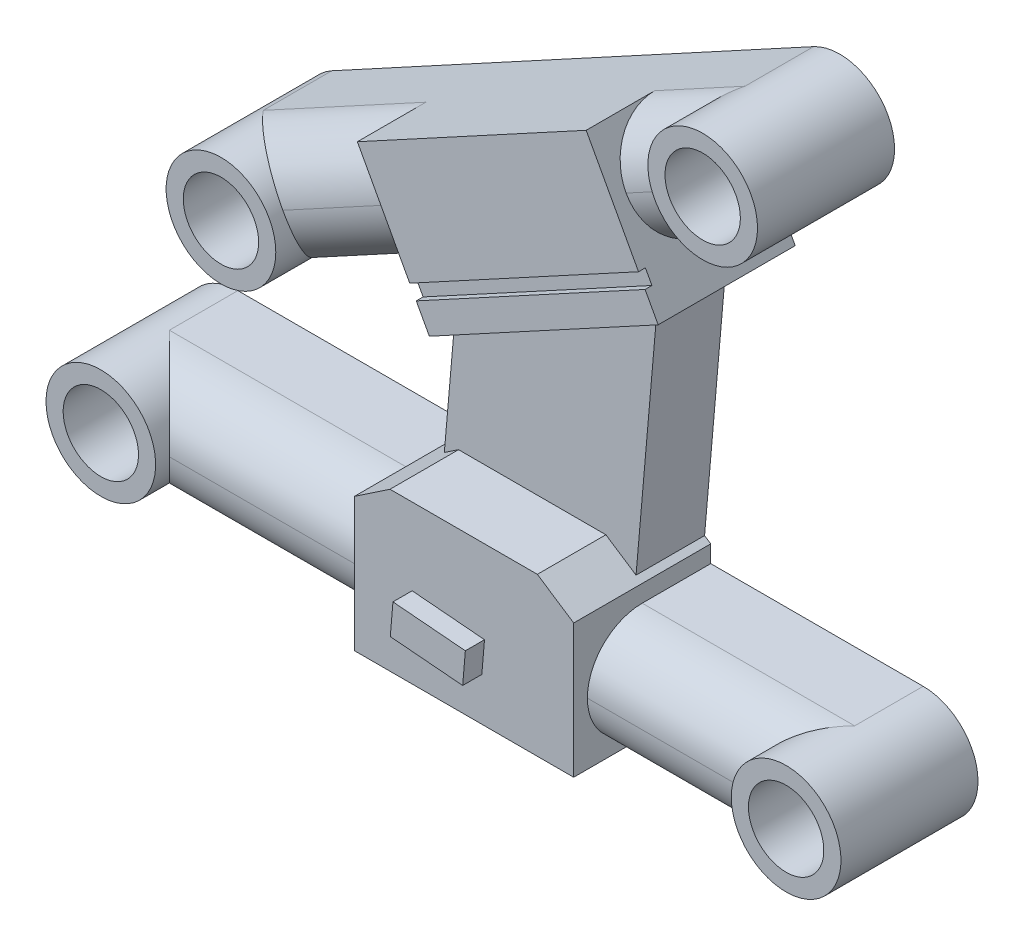
SolidWorks part; units mm, degrees
ref_plane "Front Plane" through (0, 0, 0) normal (0, 0, 1) x (1, 0, 0)
ref_plane "Top Plane" through (0, 0, 0) normal (0, 1, 0) x (1, 0, 0)
ref_plane "Right Plane" through (0, 0, 0) normal (1, 0, 0) x (0, 0, -1)
sketch "Sketch1" plane through (0, 0, 0) normal (0, 0, 1) x (1, 0, 0)
  line L0 (0, 0) -> (32, 0)
  line L1 (32, 0) -> (32, 19.5)
  line L2 (32, 19.5) -> (26.7, 23)
  line L3 (26.7, 23) -> (5.2, 23)
  line L4 (5.2, 23) -> (0, 19.5)
  line L5 (0, 19.5) -> (0, 0)
  dimension "D1" = 32
  dimension "D2" = 19.5
  dimension "D3" = 21.5
  dimension "D4" = 23
  dimension "D5" = 26.8
extrude "Boss-Extrude1" add sketch "Sketch1" along normal blind 20
sketch "Sketch2" plane through (0, 0, 0) normal (0, 0, -1) x (-1, 0, 0)
  line L0 (0, 0) -> (88.9399, 0) construction
  line L1 (88.9399, 0) -> (-120.0605, 0) construction
  line L2 (-32, 0) -> (-32, 19.5) construction
  line L3 (0, 19.5) -> (0, 0) construction
  circle A0 centre (-63, 9) radius 5.5
  circle A1 centre (-63, 9) radius 8
  circle A2 centre (37, 9) radius 5.5
  circle A3 centre (37, 9) radius 8
  dimension "D1" = 11
  dimension "D2" = 16
  dimension "D5" = 11
  dimension "D6" = 16
  dimension "D3" = 9
  dimension "D4" = 31
  dimension "D7" = 9
  dimension "D8" = 37
extrude "Boss-Extrude2" add sketch "Sketch2" against normal blind 20 separate body
sketch "Sketch4" plane through (32, 0, 0) normal (1, 0, 0) x (0, 0, -1)
  line L0 (0, 0) -> (0, 19.5) construction
  line L1 (0, 17) -> (-18, 17)
  line L2 (0, 17) -> (0, 1)
  line L3 (0, 1) -> (-18, 1)
  line L4 (-18, 17) -> (-18, 1)
  line L5 (-20, 19.5) -> (0, 19.5) construction
  dimension "D1" = 18
  dimension "D2" = 16
  dimension "D3" = 2.5
extrude "Boss-Extrude3" add sketch "Sketch4" along normal up to surface (31 mm away) up to face at (55, 9, 20)
sketch "Sketch5" plane through (0, 0, 0) normal (-1, 0, 0) x (0, 0, 1)
  line L0 (0, 19.5) -> (0, 0) construction
  line L1 (0, 17) -> (18, 17)
  line L2 (0, 17) -> (0, 1)
  line L3 (0, 1) -> (18, 1)
  line L4 (18, 17) -> (18, 1)
  line L5 (20, 19.5) -> (0, 19.5) construction
  dimension "D1" = 2.5
  dimension "D2" = 18
  dimension "D3" = 16
extrude "Boss-Extrude4" add sketch "Sketch5" along normal up to surface (37 mm away) up to face at (-45, 9, 20)
sketch "Sketch6" plane through (0, 0, 0) normal (0, 0, -1) x (-1, 0, 0)
  line L0 (-31.1, 20.0943) -> (-34.4, 57.9508)
  line L1 (-32, 19.5) -> (-26.7, 23) construction
  line L2 (-3.1254, 21.6036) -> (-5.9785, 54.3336)
  line L3 (-5.2, 23) -> (0, 19.5) construction
  line L4 (-10.9396, 45.2033) -> (-44.3289, 63.3458)
  line L5 (-44.3289, 63.3458) -> (-33.8254, 82.6765)
  line L6 (-33.8254, 82.6765) -> (-0.436, 64.5339)
  line L7 (-0.436, 64.5339) -> (-10.9396, 45.2033)
  line L8 (-32, 17) -> (-32, 19.5) construction
  line M11 (0, 19.5) -> (-5.2, 23)
  line M12 (-5.2, 23) -> (-26.7, 23)
  line M13 (-26.7, 23) -> (-32, 19.5)
  dimension "D1" = 28
  dimension "D2" = 0.9
  dimension "D3" = 38
  dimension "D4" = 2.4
  dimension "D5" = 38
  dimension "D6" = 22
  dimension "D7" = 123.5
  dimension "D8" = 11.3
extrude "Boss-Extrude5" add sketch "Sketch6" against normal blind 10 contours L2 L7 L4 L0 M13 M12 M11 region at (19.3948, 37.1745, 0)
extrude "Boss-Extrude6" add sketch "Sketch6<3>" against normal blind 20 contours L7 L6 L5 L4 region at (22.3825, 63.9399, 0)
sketch "Sketch6<3>" plane through (0, 0, 0) normal (0, 0, -1) x (-1, 0, 0) same geometry as "Sketch6"
sketch "Sketch7" plane through (0, 0, 20) normal (0, 0, 1) x (1, 0, 0)
  line L0 (-19.4685, 44.6138) -> (50.8248, 82.8087) construction
  line L3 (33.8254, 82.6765) -> (0.436, 64.5339) construction
  line L4 (0.436, 64.5339) -> (10.9396, 45.2033) construction
  line L6 (44.3289, 63.3458) -> (33.8254, 82.6765) construction
  circle A0 centre (50.8248, 82.8087) radius 5.5
  circle A1 centre (50.8248, 82.8087) radius 8
  circle A2 centre (-19.4685, 44.6138) radius 5.5
  circle A3 centre (-19.4685, 44.6138) radius 8
  dimension "D4" = 11
  dimension "D5" = 16
  dimension "D6" = 11
  dimension "D7" = 16
  dimension "D1" = 8
  dimension "D2" = 27
  dimension "D3" = 15
extrude "Boss-Extrude7" add sketch "Sketch7" against normal blind 20 separate body
sketch "Sketch8" plane through (27.409, 14.8931, 0) normal (-0.8787, -0.4774, 0) x (0, 0, 1)
  line L0 (0, 56.4956) -> (0, 44.8868) construction
  line L1 (0, 56.4956) -> (18, 56.4956)
  line L2 (0, 56.4956) -> (0, 40.4956)
  line L3 (0, 40.4956) -> (18, 40.4956)
  line L4 (18, 56.4956) -> (18, 40.4956)
  line L6 (20, 56.4956) -> (0, 56.4956) construction
  dimension "D2" = 16
  dimension "D3" = 18
extrude "Boss-Extrude8" add sketch "Sketch8" along normal up to surface (27 mm away) up to face at (-11.4685, 44.6138, 0)
sketch "Sketch9" plane through (60.7984, 33.0356, 0) normal (0.8787, 0.4774, 0) x (0, 0, -1)
  line L1 (0, 56.4956) -> (-18, 56.4956)
  line L2 (0, 56.4956) -> (0, 40.4956)
  line L3 (0, 40.4956) -> (-18, 40.4956)
  line L4 (-18, 56.4956) -> (-18, 40.4956)
  dimension "D1" = 18
  dimension "D2" = 16
extrude "Boss-Extrude9" add sketch "Sketch9" along normal up to surface (15 mm away) up to face at (58.8248, 82.8087, 0)
fillet "Fillet1" radius 8 8 edges at (47.5, 1, 18) (47.5, 17, 18) (48.0543, 72.1986, 18) (40.4154, 86.2572, 18) (-11.426, 58.0885, 18) (-3.787, 44.0299, 18) (-18.5, 1, 18) (-18.5, 17, 18)
sketch "Sketch10" plane through (0, 0, 20) normal (0, 0, 1) x (1, 0, 0)
  line L0 (9.0299, 48.7179) -> (42.4192, 66.8605)
  line L1 (0.436, 64.5339) -> (10.9396, 45.2033) construction
  line L2 (44.3289, 63.3458) -> (33.8254, 82.6765) construction
  line L3 (42.4192, 66.8605) -> (41.4643, 68.6178)
  line L4 (41.4643, 68.6178) -> (8.075, 50.4753)
  line L5 (8.075, 50.4753) -> (10.9396, 45.2033) construction
  line L6 (8.075, 50.4753) -> (9.0299, 48.7179)
  line L8 (10.9396, 45.2033) -> (44.3289, 63.3458) construction
  dimension "D1" = 2
  dimension "D2" = 4
extrude "Cut-Extrude1" cut sketch "Sketch10" against normal blind 1
sketch "Sketch11" plane through (0, 0, 20) normal (0, 0, 1) x (1, 0, 0)
  line L0 (18.9906, 10.8834) -> (18.6, 6.3)
  line L1 (18.6, 6.3) -> (8.0383, 7.2)
  line L2 (8.0383, 7.2) -> (8.4288, 11.7834)
  line L3 (8.4288, 11.7834) -> (18.9906, 10.8834)
  line L4 (0, 0) -> (32, 0) construction
  line L5 (32, 0) -> (32, 19.5) construction
  dimension "D1" = 10.6
  dimension "D2" = 4.6
  dimension "D3" = 6.3
  dimension "D4" = 7.2
  dimension "D5" = 13.4
extrude "Boss-Extrude10" add sketch "Sketch11" along normal blind 2.8
sketch "Sketch12" plane through (0, 0, 0) normal (0, 0, -1) x (-1, 0, 0)
  line L0 (-31.1, 20.0943) -> (-3.2058, 22.5259) construction
  line L1 (-3.1254, 21.6036) -> (-5.5212, 49.0876) construction
  line L2 (-25.0378, 28.8539) -> (-9.6901, 30.1918)
  line L3 (-9.6901, 30.1918) -> (-11.0796, 46.1313)
  line L4 (-11.0796, 46.1313) -> (-15.5626, 45.7405)
  line L5 (-15.5626, 45.7405) -> (-14.7376, 36.2764)
  line L6 (-14.7376, 36.2764) -> (-21.1193, 35.7201)
  line L7 (-21.1193, 35.7201) -> (-21.9443, 45.1842)
  line L8 (-21.9443, 45.1842) -> (-26.4273, 44.7934)
  line L9 (-26.4273, 44.7934) -> (-25.0378, 28.8539)
  line L10 (-25.6023, 35.3293) -> (-10.2546, 36.6672)
  line L11 (-31.1, 20.0943) -> (-34.4, 57.9508) construction
  line L12 (-17.9284, 35.9983) -> (-19.3449, 52.248) construction
  line L13 (0, 0) -> (-32, 0) construction
  line L14 (-32, 0) -> (-32, 1) construction
  line L15 (-0.1188, 13.4597) -> (0.8, 3)
  line L16 (0.8, 3) -> (16.7386, 4.4)
  line L17 (16.7386, 4.4) -> (16.3449, 8.8827)
  line L18 (16.3449, 8.8827) -> (6.8813, 8.0515)
  line L19 (6.8813, 8.0515) -> (6.3563, 14.0285)
  line L20 (6.3563, 14.0285) -> (-0.1188, 13.4597)
  line L21 (6.8813, 8.0515) -> (7.2751, 3.5688)
  line L22 (37, 1) -> (0, 1) construction
  line L23 (0, 1) -> (0, 0) construction
  line L24 (6.8813, 8.0515) -> (7.2751, 3.5688)
  circle A0 centre (-18.3626, 40.9794) radius 1.6
  circle A1 centre (-22, 9) radius 5
  circle A2 centre (11.5996, 11.4775) radius 1.605
  dimension "D7" = 3.2
  dimension "D9" = 10
  dimension "D12" = 3.21
  dimension "D1" = 8.2
  dimension "D2" = 6.8
  dimension "D3" = 5.7941
  dimension "D4" = 4.5
  dimension "D5" = 16
  dimension "D6" = 9.5
  dimension "D8" = 5
  dimension "D10" = 9
  dimension "D11" = 10
  dimension "D13" = 16
  dimension "D14" = 10.5
  dimension "D15" = 6.5
  dimension "D16" = 6
  dimension "D17" = 3
  dimension "D18" = 5
  dimension "D19" = 2
  dimension "D20" = 0.8
  dimension "D21" = 3.4
extrude "Cut-Extrude2" cut sketch "Sketch12" against normal blind 2 contours A1 region at (22, 9, 0)
extrude "Cut-Extrude3" cut sketch "Sketch12<4>" against normal blind 7 contours L21 L19 L20 L15 L16 | L10 L9 L2 L3 L6 region at (17.6462, 32.7605, 0) region at (-3.5782, 8.5142, 0)
sketch "Sketch12<4>" plane through (0, 0, 0) normal (0, 0, -1) x (-1, 0, 0) same geometry as "Sketch12"
extrude "Cut-Extrude4" cut sketch "Sketch12<6>" against normal blind 2 contours L18 L21 L16 L17 | L5 L10 L3 L4 | L9 L10 L7 L8 region at (23.7733, 40.2568, 0) region at (12.9086, 41.2039, 0) region at (-11.81, 6.2257, 0)
sketch "Sketch12<6>" plane through (0, 0, 0) normal (0, 0, -1) x (-1, 0, 0) same geometry as "Sketch12"
extrude "Cut-Extrude5" cut sketch "Sketch12<7>" against normal blind 8 contours A2 | A0 region at (18.3626, 40.9794, 0) region at (-11.5996, 11.4775, 0)
sketch "Sketch12<7>" plane through (0, 0, 0) normal (0, 0, -1) x (-1, 0, 0) same geometry as "Sketch12"
sketch "Sketch13" plane through (1.2328, -0.1075, 0) normal (-0.9962, 0.0868, 0) x (0, 0, 1)
  line L0 (0, 21.7934) -> (0, 49.3816) construction
  line L1 (4.2, 45.2934) -> (7, 45.2934)
  line L2 (4.2, 45.2934) -> (4.2, 39.4934)
  line L3 (4.2, 39.4934) -> (7, 39.4934)
  line L4 (7, 45.2934) -> (7, 39.4934)
  line L5 (10, 21.7934) -> (0, 21.7934) construction
  dimension "D1" = 5.8
  dimension "D2" = 2.8
  dimension "D3" = 4.2
  dimension "D4" = 17.7
extrude "Cut-Extrude6" cut sketch "Sketch13" against normal blind 22
sketch "Sketch14" plane through (0, 1, 0) normal (0, -1, 0) x (1, 0, 0)
  line L0 (0, 0) -> (0, 10) construction
  line L1 (-15.4, 7) -> (-9.6, 7)
  line L2 (-15.4, 7) -> (-15.4, 4.2)
  line L3 (-15.4, 4.2) -> (-9.6, 4.2)
  line L4 (-9.6, 7) -> (-9.6, 4.2)
  line L5 (-37, 0) -> (0, 0) construction
  dimension "D1" = 5.8
  dimension "D2" = 2.8
  dimension "D3" = 9.6
  dimension "D4" = 4.2
extrude "Cut-Extrude7" cut sketch "Sketch14" against normal blind 14.5
sketch "Sketch15" plane through (0, 1, 0) normal (0, -1, 0) x (1, 0, 0)
  line L0 (-9.6, 7) -> (-8.1, 7)
  line L1 (-8.1, 7) -> (-8.1, 4.2)
  line L2 (-8.1, 4.2) -> (-9.6, 4.2)
  line L3 (-9.6, 4.2) -> (-9.6, 7) construction
  line L4 (-9.6, 7) -> (-9.6, 4.2)
  dimension "D1" = 1.5
extrude "Cut-Extrude8" cut sketch "Sketch15" against normal up to surface (14.5 mm away) up to face at (-12.5, 15.5, 5.6)
